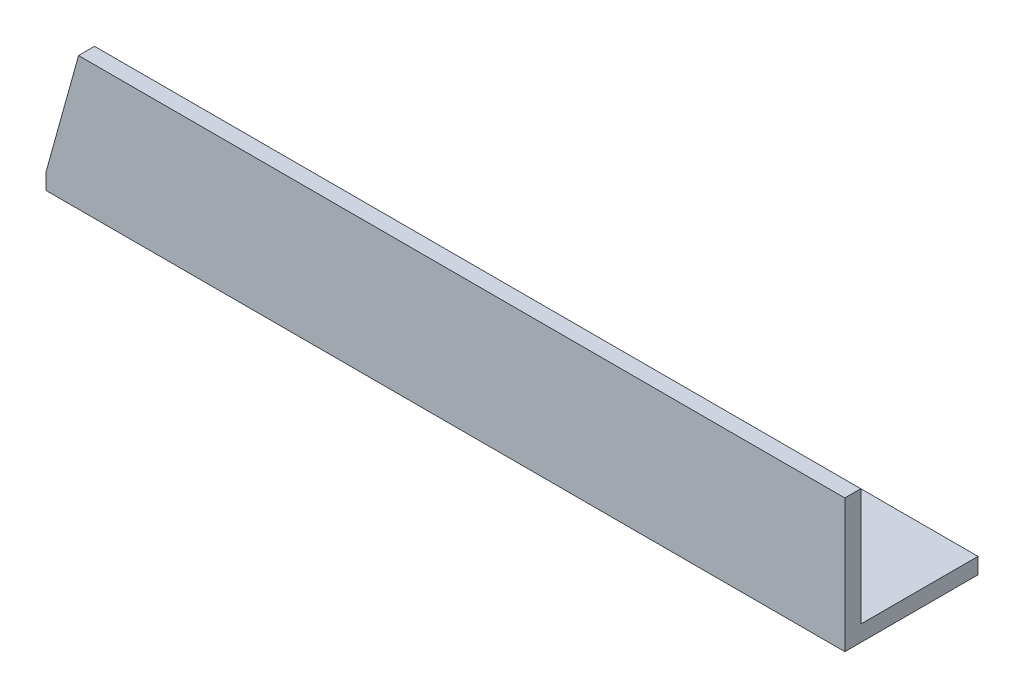
SolidWorks part; units mm, degrees
ref_plane "Спереди" through (0, 0, 0) normal (0, 0, 1) x (1, 0, 0)
ref_plane "Сверху" through (0, 0, 0) normal (0, 1, 0) x (1, 0, 0)
ref_plane "Справа" through (0, 0, 0) normal (1, 0, 0) x (0, 0, -1)
sketch "Эскиз1" plane through (0, 0, 0) normal (1, 0, 0) x (0, 0, -1)
  line L0 (0, 50) -> (0, 0)
  line L1 (0, 0) -> (50, 0)
extrude "Вытянуть-Тонкостенный1" add sketch "Эскиз1" along normal blind 300 thin thin type one direction reverse wall 6
sketch "Эскиз2" plane through (0, 0, 0) normal (0, 0, 1) x (1, 0, 0)
  line L0 (0, 50) -> (12.2265, 50)
  line L1 (300, 50) -> (0, 50) construction
  line L2 (0, 6) -> (12.2265, 50) construction
  line L3 (12.2265, 50) -> (0, 6)
  line L4 (0, 6) -> (0, 50)
extrude "Вырез-Вытянуть1" cut sketch "Эскиз2" against normal through all
